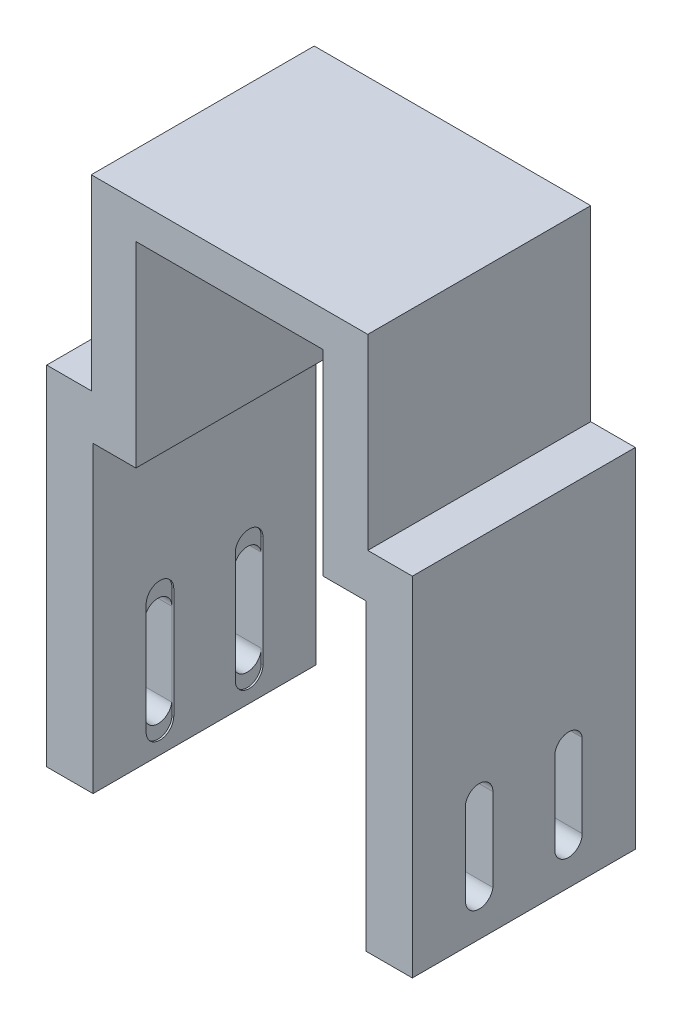
SolidWorks part; units mm, degrees
ref_plane "Front Plane" through (0, 0, 0) normal (0, 0, 1) x (1, 0, 0)
ref_plane "Top Plane" through (0, 0, 0) normal (0, 1, 0) x (1, 0, 0)
ref_plane "Right Plane" through (0, 0, 0) normal (1, 0, 0) x (0, 0, -1)
sketch "Sketch1" plane through (0, 0, 0) normal (0, 0, 1) x (1, 0, 0)
  line L0 (0, -45.472) -> (0, 45.472) construction
  line L1 (10.5, 0) -> (-10.5, 0)
  line L2 (-10.5, 0) -> (-10.5, -56.0193)
  line L3 (-10.5, -56.0193) -> (-15.5, -56.0193)
  line L4 (-15.5, -56.0193) -> (-15.5, 3.9807)
  line L5 (-15.5, 3.9807) -> (15.5, 3.9807)
  line L6 (0, 3.9807) -> (0, 0)
  line L7 (10.5, -56.0193) -> (15.5, -56.0193)
  line L8 (15.5, -56.0193) -> (15.5, 3.9807)
  line L9 (10.5, 0) -> (10.5, -56.0193)
  point P4 (0, 0)
  point P15 (0, 0)
  dimension "D1" = 15.5
  dimension "D2" = 10.5
  dimension "D3" = 60
extrude "Boss-Extrude1" add sketch "Sketch1" along normal blind 25 contours L1 L9 L7 L8 L5 L6 | L6 L5 L4 L3 L2 L1 region at (12.0523, -22.594, 0) region at (-12.0523, -22.594, 0)
sketch "Sketch3" plane through (0, 0, 0) normal (1, 0, 0) x (0, 0, -1)
  line L0 (-12.5, -56.0193) -> (-12.5, 17.5409) construction
  line L1 (-25, -56.0193) -> (0, -56.0193) construction
  line L2 (18.5623, -46.8196) -> (-43.5623, -46.8196) construction
  line L3 (-5.95, -40.62) -> (-5.95, -53.0193)
  line L4 (-9.05, -40.62) -> (-9.05, -53.0193)
  line L5 (-19.05, -40.62) -> (-19.05, -53.0193)
  line L6 (-15.95, -40.62) -> (-15.95, -53.0193)
  circle A0 centre (-7.5, -53.0193) radius 1.55
  circle A1 centre (-17.5, -53.0193) radius 1.55
  circle A2 centre (-17.5, -40.62) radius 1.55
  circle A3 centre (-7.5, -40.62) radius 1.55
  point P14 (-12.5, -46.8196)
  dimension "D1" = 3.1
  dimension "D2" = 10
  dimension "D3" = 3
extrude "Cut-Extrude1" cut sketch "Sketch3" against normal through all both and the other way through all contours A2 L5 A1 L6 | A3 | A2 | L3 A3 L4 A0 | A1 | A0 region at (0, -40.62, 7.5) region at (0, -46.8196, 7.5) region at (0, -46.8196, 17.5) region at (0, -40.62, 17.5) region at (0, -53.0193, 17.5)
sketch "Sketch5" plane through (0, 0, 0) normal (0, 0, 1) x (1, 0, 0)
  line L0 (0, 69.8628) -> (0, -69.8628) construction
  line L1 (15.5, 3.9807) -> (-15.5, 3.9807)
  line L2 (-15.5, 3.9807) -> (15.5, 3.9807) construction
  line L3 (-15.5, 3.9807) -> (-15.5, -17)
  line L4 (-15.5, -56.0193) -> (-15.5, 3.9807) construction
  line L5 (-15.5, -17) -> (-20.5, -17)
  line L6 (-20.5, -17) -> (-20.5, -56.0193)
  line L7 (-20.5, -56.0193) -> (-15.5, -56.0193)
  line L8 (-15.5, -56.0193) -> (-15.5, -22)
  line L9 (-15.5, -22) -> (-10.5, -22)
  line L10 (-10.5, 0) -> (-10.5, -56.0193) construction
  line L11 (-10.5, -22) -> (-10.5, 0)
  line L12 (-10.5, 0) -> (0, 0)
  line L13 (10.5, 0) -> (-10.5, 0) construction
  line L14 (20.5, -56.0193) -> (15.5, -56.0193)
  line L15 (10.5, -22) -> (10.5, 0)
  line L16 (15.5, -56.0193) -> (15.5, -22)
  line L17 (20.5, -17) -> (20.5, -56.0193)
  line L18 (15.5, 3.9807) -> (15.5, -17)
  line L19 (15.5, -22) -> (10.5, -22)
  line L20 (15.5, -17) -> (20.5, -17)
  line L21 (15.5, -17) -> (15.5, -22)
  line L22 (-15.5, -17) -> (-15.5, -22)
  point P4 (0, 0)
  point P33 (0, 3.9807)
  dimension "D1" = 5
  dimension "D2" = 5
  dimension "D3" = 22
extrude "Boss-Extrude2" add sketch "Sketch5" along normal blind 25 contours L20 L21 L16 L14 L17 | L22 L5 L6 L7 L8 region at (-18, -36.5096, 0) region at (18, -36.5096, 0)
sketch "Sketch6" plane through (0, 0, 0) normal (0, 0, 1) x (1, 0, 0)
  line L0 (0, 62.4318) -> (0, -62.4318) construction
  line L1 (10.5, -56.0193) -> (15.3, -56.0193)
  line L2 (10.5, -56.0193) -> (10.5, -22)
  line L3 (10.5, -22) -> (15.3, -22)
  line L4 (15.3, -56.0193) -> (15.3, -22)
  line L6 (15.5, -17) -> (20.5, -17) construction
  line L7 (-10.5, -22) -> (-15.3, -22)
  line L8 (-15.3, -56.0193) -> (-15.3, -22)
  line L9 (-10.5, -56.0193) -> (-15.3, -56.0193)
  line L10 (-10.5, -56.0193) -> (-10.5, -22)
  point P8 (0, 0)
  dimension "D1" = 4.8
  dimension "D2" = 5
extrude "Cut-Extrude2" cut sketch "Sketch6" against normal through all and the other way through all
sketch "Sketch7" plane through (0, 0, 0) normal (1, 0, 0) x (0, 0, -1)
  line L0 (-12.5, 3.9807) -> (-12.5, -58.7393) construction
  line L1 (-25, 3.9807) -> (0, 3.9807) construction
  line L3 (-25, -56.0193) -> (0, -56.0193) construction
  line L4 (-5.95, -42.1996) -> (-5.95, -51.5193)
  line L5 (-9.0322, -42.4337) -> (-9.0322, -51.7534)
  line L6 (-19.05, -42.1996) -> (-19.05, -51.5193)
  line L7 (-15.9678, -42.4337) -> (-15.9678, -51.7534)
  circle A0 centre (-7.5, -51.5193) radius 1.55
  circle A1 centre (-17.5, -51.5193) radius 1.55
  circle A2 centre (-7.4822, -42.4337) radius 1.55
  circle A3 centre (-17.5178, -42.4337) radius 1.55
  dimension "D1" = 3.1
  dimension "D4" = 3.1
  dimension "D2" = 10
  dimension "D3" = 4.5
extrude "Cut-Extrude3" cut sketch "Sketch7" against normal through all both and the other way through all contours L4 A2 | A2 L5 A0 L4 | A0 L5 | A1 L7 | L7 A3 L6 A1 | A3 L6 region at (0, -42.4337, 7.4833) region at (0, -46.9765, 7.4911) region at (0, -51.5193, 7.4989) region at (0, -42.4337, 17.5167) region at (0, -46.9765, 17.5089) region at (0, -51.5193, 17.5011)
